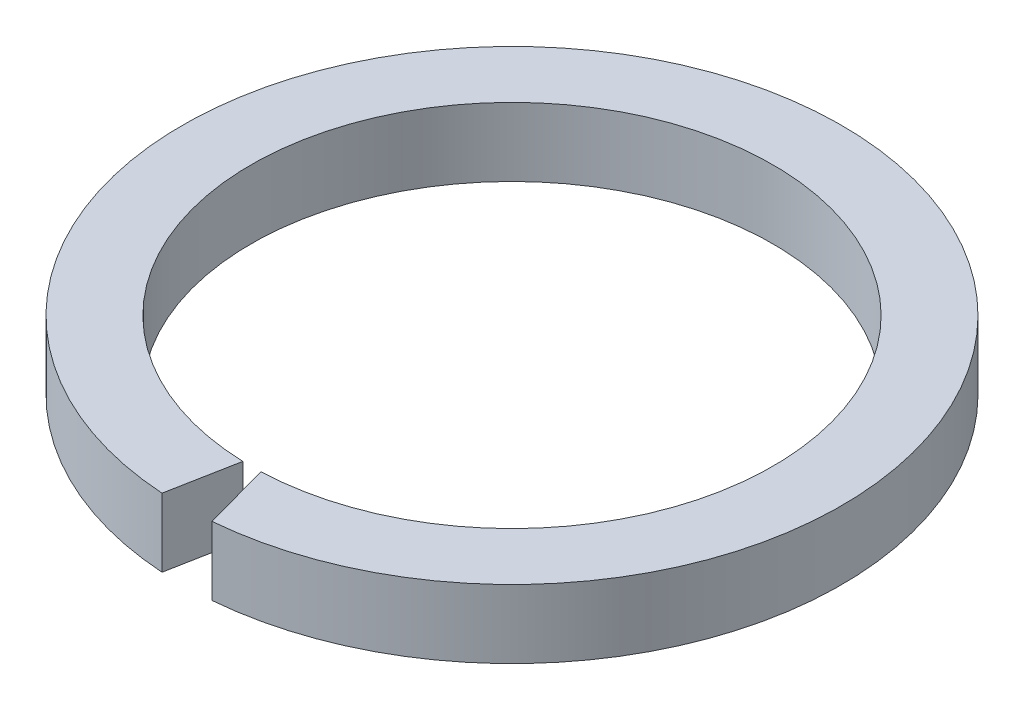
SolidWorks part; units mm, degrees
ref_plane "Front Plane" through (0, 0, 0) normal (0, 0, 1) x (1, 0, 0)
ref_plane "Top Plane" through (0, 0, 0) normal (0, 1, 0) x (1, 0, 0)
ref_plane "Right Plane" through (0, 0, 0) normal (1, 0, 0) x (0, 0, -1)
sketch "Sketch1" plane through (0, 0, 0) normal (0, 1, 0) x (1, 0, 0)
  circle A0 centre (0, 0) radius 19.05
  circle A1 centre (0, 0) radius 24.05
extrude "Boss-Extrude1" add sketch "Sketch1" along normal blind 5
sketch "Sketch3" plane through (0, 0, 0) normal (0, 1, 0) x (1, 0, 0)
  line L0 (0, 0) -> (0, -27.1481) construction
  line L1 (-1.6979, -24.8296) -> (2.2856, -24.8296)
  line L2 (0, -17.9217) -> (-0.3882, -17.9217)
  line L3 (0, -17.9217) -> (0.4279, -17.9217)
  line L4 (0.4279, -17.9217) -> (2.2856, -24.8296)
  line L5 (-1.6979, -24.8296) -> (-0.3882, -17.9217)
extrude "Cut-Extrude2" cut sketch "Sketch3" against normal blind 12 and the other way blind 15
